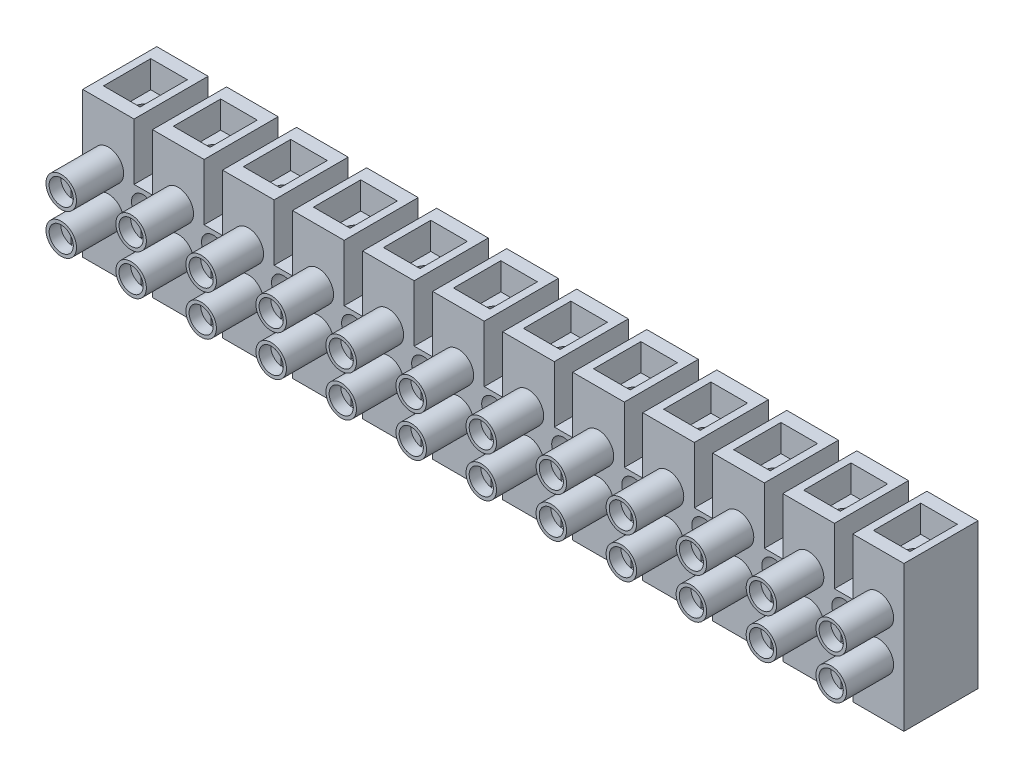
SolidWorks part; units mm, degrees
ref_plane "Front Plane" through (0, 0, 0) normal (0, 0, 1) x (1, 0, 0)
ref_plane "Top Plane" through (0, 0, 0) normal (0, 1, 0) x (1, 0, 0)
ref_plane "Right Plane" through (0, 0, 0) normal (1, 0, 0) x (0, 0, -1)
sketch "Sketch1" plane through (0, 0, 0) normal (0, 0, 1) x (1, 0, 0)
  line L1 (0, 16.9545) -> (95.758, 16.9545)
  line L2 (0, 16.9545) -> (0, 0)
  line L3 (0, 0) -> (95.758, 0)
  line L4 (95.758, 16.9545) -> (95.758, 0)
  dimension "D1" = 95.758
  dimension "D2" = 16.9545
extrude "Boss-Extrude1" add sketch "Sketch1" along normal blind 8.636
sketch "Sketch2" plane through (0, 0, 8.636) normal (0, 0, 1) x (1, 0, 0)
  line L0 (0, 8.4773) -> (95.758, 8.4773) construction
  line L1 (0, 16.9545) -> (0, 0) construction
  line L2 (95.758, 0) -> (95.758, 16.9545) construction
  line L3 (22.3202, 16.9545) -> (24.4666, 16.9545)
  line L4 (5.988, 16.9545) -> (8.1343, 16.9545)
  line L5 (5.988, 16.9545) -> (5.9881, 10.3505)
  line L6 (5.9881, 10.3505) -> (8.1343, 10.3505)
  line L7 (8.1343, 16.9545) -> (8.1343, 10.3505)
  line L8 (14.1542, 16.9545) -> (16.3005, 16.9545)
  line L9 (95.758, 16.9545) -> (0, 16.9545) construction
  line L10 (7.0612, 16.9545) -> (7.0612, 0) construction
  line L11 (15.2273, 16.9545) -> (15.2273, 0) construction
  line L12 (23.3934, 16.9545) -> (23.3934, 0) construction
  line L13 (31.5595, 16.9545) -> (31.5595, 0) construction
  line L14 (39.7256, 16.9545) -> (39.7256, 0) construction
  line L15 (47.8917, 16.9545) -> (47.8917, 0) construction
  line L16 (56.0578, 16.9545) -> (56.0578, 0) construction
  line L17 (64.2239, 16.9545) -> (64.2239, 0) construction
  line L18 (72.39, 16.9545) -> (72.39, 0) construction
  line L19 (88.7222, 16.9545) -> (88.7222, 0) construction
  line L20 (80.5561, 16.9545) -> (80.5561, 0) construction
  line L21 (0, 0) -> (95.758, 0) construction
  line L22 (14.1542, 16.9545) -> (14.1542, 10.3505)
  line L23 (14.1542, 10.3505) -> (16.3005, 10.3505)
  line L24 (16.3005, 16.9545) -> (16.3005, 10.3505)
  line L25 (22.3202, 16.9545) -> (22.3203, 10.3505)
  line L26 (22.3203, 10.3505) -> (24.4666, 10.3505)
  line L27 (24.4666, 16.9545) -> (24.4666, 10.3505)
  line L28 (30.4864, 16.9545) -> (32.6326, 16.9545)
  line L29 (30.4864, 16.9545) -> (30.4864, 10.3505)
  line L30 (30.4864, 10.3505) -> (32.6327, 10.3505)
  line L31 (32.6326, 16.9545) -> (32.6327, 10.3505)
  line L32 (38.6525, 16.9545) -> (40.7988, 16.9545)
  line L33 (38.6525, 16.9545) -> (38.6525, 10.3505)
  line L34 (38.6525, 10.3505) -> (40.7988, 10.3505)
  line L35 (40.7988, 16.9545) -> (40.7988, 10.3505)
  line L36 (46.8186, 16.9545) -> (48.9648, 16.9545)
  line L37 (46.8186, 16.9545) -> (46.8186, 10.3505)
  line L38 (46.8186, 10.3505) -> (48.9649, 10.3505)
  line L39 (48.9648, 16.9545) -> (48.9649, 10.3505)
  line L40 (54.9847, 16.9545) -> (57.131, 16.9545)
  line L41 (54.9847, 16.9545) -> (54.9847, 10.3505)
  line L42 (54.9847, 10.3505) -> (57.131, 10.3505)
  line L43 (57.131, 16.9545) -> (57.131, 10.3505)
  line L44 (63.1508, 16.9545) -> (65.2971, 16.9545)
  line L45 (63.1508, 16.9545) -> (63.1508, 10.3505)
  line L46 (63.1508, 10.3505) -> (65.2971, 10.3505)
  line L47 (65.2971, 16.9545) -> (65.2971, 10.3505)
  line L48 (71.3169, 16.9545) -> (73.4631, 16.9545)
  line L49 (71.3169, 16.9545) -> (71.3169, 10.3505)
  line L50 (71.3169, 10.3505) -> (73.4631, 10.3505)
  line L51 (73.4631, 16.9545) -> (73.4631, 10.3505)
  line L52 (79.483, 16.9545) -> (81.6292, 16.9545)
  line L53 (79.483, 16.9545) -> (79.483, 10.3505)
  line L54 (79.483, 10.3505) -> (81.6293, 10.3505)
  line L55 (81.6292, 16.9545) -> (81.6293, 10.3505)
  line L56 (87.6491, 16.9545) -> (89.7953, 16.9545)
  line L57 (87.6491, 16.9545) -> (87.6491, 10.3505)
  line L58 (87.6491, 10.3505) -> (89.7953, 10.3505)
  line L59 (89.7953, 16.9545) -> (89.7953, 10.3505)
  line L60 (5.988, 6.604) -> (8.1343, 6.604)
  line L61 (5.988, 6.604) -> (5.9881, 0)
  line L62 (5.9881, 0) -> (8.1343, 0)
  line L63 (8.1343, 6.604) -> (8.1343, 0)
  line L64 (14.1542, 6.604) -> (16.3005, 6.604)
  line L65 (14.1542, 6.604) -> (14.1542, 0)
  line L66 (14.1542, 0) -> (16.3005, 0)
  line L67 (16.3005, 6.604) -> (16.3005, 0)
  line L68 (22.3203, 6.604) -> (24.4666, 6.604)
  line L69 (22.3203, 6.604) -> (22.3203, 0)
  line L70 (22.3203, 0) -> (24.4666, 0)
  line L71 (24.4666, 6.604) -> (24.4666, 0)
  line L72 (30.4864, 6.604) -> (32.6326, 6.604)
  line L73 (30.4864, 6.604) -> (30.4864, 0)
  line L74 (30.4864, 0) -> (32.6326, 0)
  line L75 (32.6326, 6.604) -> (32.6326, 0)
  line L76 (38.6525, 6.604) -> (40.7987, 6.604)
  line L77 (38.6525, 6.604) -> (38.6525, 0)
  line L78 (38.6525, 0) -> (40.7987, 0)
  line L79 (40.7987, 6.604) -> (40.7987, 0)
  line L80 (48.9649, 6.604) -> (46.8186, 6.604)
  line L81 (48.9649, 6.604) -> (48.9649, 0)
  line L82 (48.9649, 0) -> (46.8186, 0)
  line L83 (46.8186, 6.604) -> (46.8186, 0)
  line L84 (57.131, 6.604) -> (54.9847, 6.604)
  line L85 (57.131, 6.604) -> (57.131, 0)
  line L86 (57.131, 0) -> (54.9847, 0)
  line L87 (54.9847, 6.604) -> (54.9847, 0)
  line L88 (63.1508, 6.604) -> (65.2971, 6.604)
  line L89 (63.1508, 6.604) -> (63.1508, 0)
  line L90 (63.1508, 0) -> (65.2971, 0)
  line L91 (65.2971, 6.604) -> (65.2971, 0)
  line L92 (71.3169, 6.604) -> (73.4631, 6.604)
  line L93 (71.3169, 6.604) -> (71.3169, 0)
  line L94 (71.3169, 0) -> (73.4632, 0)
  line L95 (73.4631, 6.604) -> (73.4632, 0)
  line L96 (79.483, 6.604) -> (81.6292, 6.604)
  line L97 (79.483, 6.604) -> (79.483, 0)
  line L98 (79.483, 0) -> (81.6293, 0)
  line L99 (81.6292, 6.604) -> (81.6293, 0)
  line L100 (89.7953, 6.604) -> (87.6491, 6.604)
  line L101 (89.7953, 6.604) -> (89.7953, 0)
  line L102 (89.7953, 0) -> (87.6491, 0)
  line L103 (87.6491, 6.604) -> (87.6491, 0)
  circle A0 centre (15.2273, 8.4773) radius 1.3716
  circle A1 centre (23.3934, 8.4773) radius 1.3716
  circle A2 centre (31.5595, 8.4773) radius 1.3716
  circle A3 centre (39.7256, 8.4773) radius 1.3716
  circle A4 centre (47.8917, 8.4773) radius 1.3716
  circle A5 centre (56.0578, 8.4773) radius 1.3716
  circle A6 centre (7.0612, 8.4773) radius 1.3716
  circle A7 centre (64.2239, 8.4773) radius 1.3716
  circle A8 centre (72.39, 8.4773) radius 1.3716
  circle A9 centre (80.5561, 8.4773) radius 1.3716
  circle A10 centre (88.7222, 8.4773) radius 1.3716
  dimension "D1" = 2.7432
  dimension "D2" = 7.0358
  dimension "D3" = 8.1661
  dimension "D4" = 8.1661
  dimension "D5" = 8.1661
  dimension "D6" = 8.1661
  dimension "D7" = 8.1661
  dimension "D8" = 8.1661
  dimension "D9" = 8.1661
  dimension "D10" = 8.1661
  dimension "D11" = 8.1661
  dimension "D12" = 8.1661
  dimension "D13" = 2.1463
  dimension "D14" = 6.604
extrude "Cut-Extrude2" cut sketch "Sketch2" against normal up to surface (8.636 mm away) up to face at (47.879, 8.4773, 0)
sketch "Sketch3" plane through (0, 0, 8.636) normal (0, 0, 1) x (1, 0, 0)
  line L0 (0, 6.1087) -> (95.758, 6.1087) construction
  line L1 (79.483, 16.9545) -> (73.4631, 16.9545) construction
  line L2 (0, 16.9545) -> (0, 0) construction
  line L3 (95.758, 0) -> (95.758, 16.9545) construction
  line L4 (95.758, 10.8458) -> (0, 10.8458) construction
  line L5 (47.879, 10.8458) -> (47.879, 6.1087) construction
  line L6 (95.758, 8.4773) -> (0, 8.4773) construction
  line L7 (92.7767, 16.9545) -> (92.7767, 0) construction
  line L8 (84.6392, 16.9545) -> (84.6392, 0) construction
  line L9 (76.4731, 16.9545) -> (76.4731, 0) construction
  line L10 (68.307, 16.9545) -> (68.307, 0) construction
  line L11 (60.1409, 16.9545) -> (60.1409, 0) construction
  line L12 (51.9748, 16.9545) -> (51.9748, 0) construction
  line L13 (43.8087, 16.9545) -> (43.8087, 0) construction
  line L14 (35.6425, 16.9545) -> (35.6425, 0) construction
  line L15 (27.4765, 16.9545) -> (27.4765, 0) construction
  line L16 (19.3103, 16.9545) -> (19.3104, 0) construction
  line L17 (11.1442, 16.9545) -> (11.1443, 0) construction
  line L18 (2.994, 16.9545) -> (2.994, 0) construction
  line L19 (5.988, 16.9545) -> (0, 16.9545) construction
  line L20 (0, 0) -> (5.9881, 0) construction
  line L21 (14.1542, 16.9545) -> (8.1343, 16.9545) construction
  line L22 (8.1343, 0) -> (14.1542, 0) construction
  line L23 (22.3202, 16.9545) -> (16.3005, 16.9545) construction
  line L24 (16.3005, 0) -> (22.3203, 0) construction
  line L25 (30.4864, 16.9545) -> (24.4666, 16.9545) construction
  line L26 (24.4666, 0) -> (30.4864, 0) construction
  line L27 (38.6525, 16.9545) -> (32.6326, 16.9545) construction
  line L28 (32.6326, 0) -> (38.6525, 0) construction
  line L29 (46.8186, 16.9545) -> (40.7988, 16.9545) construction
  line L30 (40.7987, 0) -> (46.8186, 0) construction
  line L31 (54.9847, 16.9545) -> (48.9648, 16.9545) construction
  line L32 (48.9649, 0) -> (54.9847, 0) construction
  line L33 (63.1508, 16.9545) -> (57.131, 16.9545) construction
  line L34 (57.131, 0) -> (63.1508, 0) construction
  line L35 (71.3169, 16.9545) -> (65.2971, 16.9545) construction
  line L36 (65.2971, 0) -> (71.3169, 0) construction
  line L37 (73.4632, 0) -> (79.483, 0) construction
  line L38 (87.6491, 16.9545) -> (81.6292, 16.9545) construction
  line L39 (81.6293, 0) -> (87.6491, 0) construction
  line L40 (95.758, 16.9545) -> (89.7953, 16.9545) construction
  line L41 (89.7953, 0) -> (95.758, 0) construction
  circle A0 centre (92.7767, 6.1087) radius 1.778
  circle A1 centre (11.1443, 10.8458) radius 1.778
  circle A2 centre (19.3103, 10.8458) radius 1.778
  circle A3 centre (27.4765, 10.8458) radius 1.778
  circle A4 centre (35.6425, 10.8458) radius 1.778
  circle A5 centre (43.8087, 10.8458) radius 1.778
  circle A6 centre (51.9748, 10.8458) radius 1.778
  circle A7 centre (60.1409, 10.8458) radius 1.778
  circle A8 centre (68.307, 10.8458) radius 1.778
  circle A9 centre (76.4731, 10.8458) radius 1.778
  circle A10 centre (84.6392, 10.8458) radius 1.778
  circle A11 centre (92.7767, 10.8458) radius 1.778
  circle A12 centre (2.994, 10.8458) radius 1.778
  circle A13 centre (2.994, 6.1087) radius 1.778
  circle A14 centre (11.1443, 6.1087) radius 1.778
  circle A15 centre (19.3103, 6.1087) radius 1.778
  circle A16 centre (27.4765, 6.1087) radius 1.778
  circle A17 centre (35.6426, 6.1087) radius 1.778
  circle A18 centre (43.8087, 6.1087) radius 1.778
  circle A19 centre (51.9748, 6.1087) radius 1.778
  circle A20 centre (60.1409, 6.1087) radius 1.778
  circle A21 centre (68.307, 6.1087) radius 1.778
  circle A22 centre (76.4731, 6.1087) radius 1.778
  circle A23 centre (84.6392, 6.1087) radius 1.778
  point P16 (47.879, 8.4773)
  dimension "D1" = 3.556
  dimension "D2" = 4.7371
extrude "Boss-Extrude2" add sketch "Sketch3" along normal blind 5.4991
sketch "Sketch4" plane through (0, 0, 14.1351) normal (0, 0, 1) x (1, 0, 0)
  circle A0 centre (11.1443, 6.1087) radius 1.4097
  circle A1 centre (19.3103, 6.1087) radius 1.4097
  circle A2 centre (27.4765, 6.1087) radius 1.4097
  circle A3 centre (35.6426, 6.1087) radius 1.4097
  circle A4 centre (43.8087, 6.1087) radius 1.4097
  circle A5 centre (51.9748, 6.1087) radius 1.4097
  circle A6 centre (60.1409, 6.1087) radius 1.4097
  circle A7 centre (68.307, 6.1087) radius 1.4097
  circle A8 centre (76.4731, 6.1087) radius 1.4097
  circle A9 centre (84.6392, 6.1087) radius 1.4097
  circle A10 centre (92.7767, 6.1087) radius 1.4097
  circle A11 centre (92.7767, 10.8458) radius 1.4097
  circle A12 centre (84.6392, 10.8458) radius 1.4097
  circle A13 centre (76.4731, 10.8458) radius 1.4097
  circle A14 centre (68.307, 10.8458) radius 1.4097
  circle A15 centre (60.1409, 10.8458) radius 1.4097
  circle A16 centre (51.9748, 10.8458) radius 1.4097
  circle A17 centre (43.8087, 10.8458) radius 1.4097
  circle A18 centre (35.6425, 10.8458) radius 1.4097
  circle A19 centre (27.4765, 10.8458) radius 1.4097
  circle A20 centre (19.3103, 10.8458) radius 1.4097
  circle A21 centre (11.1443, 10.8458) radius 1.4097
  circle A22 centre (2.994, 10.8458) radius 1.4097
  circle A23 centre (2.994, 6.1087) radius 1.4097
  circle A26 centre (92.7767, 10.8458) radius 1.778 construction
  circle A27 centre (84.6392, 10.8458) radius 1.778 construction
  circle A28 centre (76.4731, 10.8458) radius 1.778 construction
  circle A29 centre (68.307, 10.8458) radius 1.778 construction
  circle A30 centre (60.1409, 10.8458) radius 1.778 construction
  circle A31 centre (51.9748, 10.8458) radius 1.778 construction
  circle A32 centre (43.8087, 10.8458) radius 1.778 construction
  circle A33 centre (35.6425, 10.8458) radius 1.778 construction
  circle A34 centre (27.4765, 10.8458) radius 1.778 construction
  circle A35 centre (19.3103, 10.8458) radius 1.778 construction
  circle A36 centre (11.1443, 10.8458) radius 1.778 construction
  circle A37 centre (2.994, 10.8458) radius 1.778 construction
  circle A38 centre (2.994, 6.1087) radius 1.778 construction
  circle A39 centre (11.1443, 6.1087) radius 1.778 construction
  circle A40 centre (19.3103, 6.1087) radius 1.778 construction
  circle A41 centre (27.4765, 6.1087) radius 1.778 construction
  circle A42 centre (35.6426, 6.1087) radius 1.778 construction
  circle A43 centre (43.8087, 6.1087) radius 1.778 construction
  circle A44 centre (51.9748, 6.1087) radius 1.778 construction
  circle A45 centre (60.1409, 6.1087) radius 1.778 construction
  circle A46 centre (68.307, 6.1087) radius 1.778 construction
  circle A47 centre (76.4731, 6.1087) radius 1.778 construction
  circle A48 centre (84.6392, 6.1087) radius 1.778 construction
  circle A49 centre (92.7767, 6.1087) radius 1.778 construction
  dimension "D1" = 2.8194
extrude "Cut-Extrude3" cut sketch "Sketch4" against normal blind 1.3589
sketch "Sketch5" plane through (0, 0, 0) normal (0, -1, 0) x (1, 0, 0)
  line L0 (27.4765, 8.636) -> (27.4765, 0) construction
  line L1 (35.6425, 8.636) -> (35.6425, 0) construction
  line L2 (43.8087, 8.636) -> (43.8087, 0) construction
  line L3 (51.9748, 8.636) -> (51.9748, 0) construction
  line L4 (60.1409, 8.636) -> (60.1409, 0) construction
  line L5 (68.307, 8.636) -> (68.307, 0) construction
  line L6 (76.4731, 8.636) -> (76.4731, 0) construction
  line L7 (84.6392, 8.636) -> (84.6392, 0) construction
  line L8 (92.7767, 8.636) -> (92.7767, 0) construction
  line L9 (19.3104, 8.636) -> (19.3104, 0) construction
  line L10 (11.1443, 8.636) -> (11.1443, 0) construction
  line L11 (2.994, 8.636) -> (2.994, 0) construction
  line L12 (0, 8.636) -> (5.9881, 8.636) construction
  line L13 (0, 0) -> (5.9881, 0) construction
  line L14 (8.1343, 8.636) -> (14.1542, 8.636) construction
  line L15 (8.1343, 0) -> (14.1542, 0) construction
  line L16 (16.3005, 8.636) -> (22.3203, 8.636) construction
  line L17 (16.3005, 0) -> (22.3203, 0) construction
  line L18 (24.4666, 8.636) -> (30.4864, 8.636) construction
  line L19 (24.4666, 0) -> (30.4864, 0) construction
  line L20 (32.6326, 8.636) -> (38.6525, 8.636) construction
  line L21 (40.7987, 8.636) -> (46.8186, 8.636) construction
  line L22 (48.9649, 8.636) -> (54.9847, 8.636) construction
  line L23 (57.131, 8.636) -> (63.1508, 8.636) construction
  line L24 (65.2971, 8.636) -> (71.3169, 8.636) construction
  line L25 (73.4632, 8.636) -> (79.483, 8.636) construction
  line L26 (81.6293, 8.636) -> (87.6491, 8.636) construction
  line L27 (89.7953, 8.636) -> (95.758, 8.636) construction
  line L28 (32.6326, 0) -> (38.6525, 0) construction
  line L29 (40.7987, 0) -> (46.8186, 0) construction
  line L30 (48.9649, 0) -> (54.9847, 0) construction
  line L31 (57.131, 0) -> (63.1508, 0) construction
  line L32 (65.2971, 0) -> (71.3169, 0) construction
  line L33 (73.4632, 0) -> (79.483, 0) construction
  line L34 (81.6293, 0) -> (87.6491, 0) construction
  line L35 (89.7953, 0) -> (95.758, 0) construction
  line L36 (9.0107, 7.0739) -> (13.2779, 7.0739)
  line L37 (0.8604, 7.0739) -> (5.1276, 7.0739)
  line L38 (0.8604, 7.0739) -> (0.8604, 1.5621)
  line L39 (0.8604, 1.5621) -> (5.1276, 1.5621)
  line L40 (5.1276, 7.0739) -> (5.1276, 1.5621)
  line L41 (9.0107, 7.0739) -> (9.0107, 1.5621)
  line L42 (9.0107, 1.5621) -> (13.2779, 1.5621)
  line L43 (13.2779, 7.0739) -> (13.2779, 1.5621)
  line L44 (25.3429, 7.0739) -> (29.6101, 7.0739)
  line L45 (25.3429, 7.0739) -> (25.3429, 1.5621)
  line L46 (25.3429, 1.5621) -> (29.6101, 1.5621)
  line L47 (29.6101, 7.0739) -> (29.6101, 1.5621)
  line L48 (33.5089, 7.0739) -> (37.7761, 7.0739)
  line L49 (33.5089, 7.0739) -> (33.5089, 1.5621)
  line L50 (33.5089, 1.5621) -> (37.7761, 1.5621)
  line L51 (37.7761, 7.0739) -> (37.7761, 1.5621)
  line L52 (41.6751, 7.0739) -> (45.9423, 7.0739)
  line L53 (41.6751, 7.0739) -> (41.6751, 1.5621)
  line L54 (41.6751, 1.5621) -> (45.9423, 1.5621)
  line L55 (45.9423, 7.0739) -> (45.9423, 1.5621)
  line L56 (17.1768, 7.0739) -> (21.444, 7.0739)
  line L57 (17.1768, 7.0739) -> (17.1768, 1.5621)
  line L58 (17.1768, 1.5621) -> (21.444, 1.5621)
  line L59 (21.444, 7.0739) -> (21.444, 1.5621)
  line L60 (66.1734, 7.0739) -> (70.4406, 7.0739)
  line L61 (66.1734, 7.0739) -> (66.1734, 1.5621)
  line L62 (66.1734, 1.5621) -> (70.4406, 1.5621)
  line L63 (70.4406, 7.0739) -> (70.4406, 1.5621)
  line L64 (74.3395, 7.0739) -> (78.6067, 7.0739)
  line L65 (74.3395, 7.0739) -> (74.3395, 1.5621)
  line L66 (74.3395, 1.5621) -> (78.6067, 1.5621)
  line L67 (78.6067, 7.0739) -> (78.6067, 1.5621)
  line L68 (82.5056, 7.0739) -> (86.7728, 7.0739)
  line L69 (82.5056, 7.0739) -> (82.5056, 1.5621)
  line L70 (82.5056, 1.5621) -> (86.7728, 1.5621)
  line L71 (86.7728, 7.0739) -> (86.7728, 1.5621)
  line L72 (49.8411, 7.0739) -> (54.1084, 7.0739)
  line L73 (49.8411, 7.0739) -> (49.8411, 1.5621)
  line L74 (49.8411, 1.5621) -> (54.1084, 1.5621)
  line L75 (54.1084, 7.0739) -> (54.1084, 1.5621)
  line L76 (90.6431, 7.0739) -> (94.9103, 7.0739)
  line L77 (90.6431, 7.0739) -> (90.6431, 1.5621)
  line L78 (90.6431, 1.5621) -> (94.9103, 1.5621)
  line L79 (94.9103, 7.0739) -> (94.9103, 1.5621)
  line L80 (58.0073, 7.0739) -> (62.2745, 7.0739)
  line L81 (58.0073, 7.0739) -> (58.0073, 1.5621)
  line L82 (58.0073, 1.5621) -> (62.2745, 1.5621)
  line L83 (62.2745, 7.0739) -> (62.2745, 1.5621)
  line L92 (0, 4.318) -> (5.9881, 4.318) construction
  line L93 (8.1344, 4.318) -> (14.1542, 4.318) construction
  line L94 (16.3005, 4.318) -> (22.3203, 4.318) construction
  line L95 (24.4666, 4.318) -> (30.4864, 4.318) construction
  line L96 (32.6326, 4.318) -> (38.6525, 4.318) construction
  line L97 (40.7987, 4.318) -> (46.8186, 4.318) construction
  line L98 (48.9649, 4.318) -> (54.9847, 4.318) construction
  line L99 (57.131, 4.318) -> (63.1508, 4.318) construction
  line L100 (65.2971, 4.318) -> (71.3169, 4.318) construction
  line L101 (73.4631, 4.318) -> (79.483, 4.318) construction
  line L102 (81.6293, 4.318) -> (87.6491, 4.318) construction
  line L103 (89.7953, 4.318) -> (95.758, 4.318) construction
  line L104 (0, 8.636) -> (0, 0) construction
  line L105 (5.9881, 0) -> (5.9881, 8.636) construction
  line L106 (8.1344, 0) -> (8.1344, 8.636) construction
  line L107 (14.1542, 0) -> (14.1542, 8.636) construction
  line L108 (16.3005, 0) -> (16.3005, 8.636) construction
  line L109 (22.3203, 0) -> (22.3203, 8.636) construction
  line L110 (24.4666, 0) -> (24.4666, 8.636) construction
  line L111 (30.4864, 0) -> (30.4864, 8.636) construction
  line L112 (32.6326, 0) -> (32.6326, 8.636) construction
  line L113 (38.6525, 0) -> (38.6525, 8.636) construction
  line L114 (40.7987, 0) -> (40.7987, 8.636) construction
  line L115 (46.8186, 0) -> (46.8186, 8.636) construction
  line L116 (48.9649, 0) -> (48.9649, 8.636) construction
  line L117 (54.9847, 0) -> (54.9847, 8.636) construction
  line L118 (57.131, 0) -> (57.131, 8.636) construction
  line L119 (63.1508, 0) -> (63.1508, 8.636) construction
  line L120 (65.2971, 0) -> (65.2971, 8.636) construction
  line L121 (71.3169, 0) -> (71.3169, 8.636) construction
  line L122 (73.4631, 0) -> (73.4631, 8.636) construction
  line L123 (79.483, 0) -> (79.483, 8.636) construction
  line L124 (81.6293, 0) -> (81.6293, 8.636) construction
  line L125 (87.6491, 0) -> (87.6491, 8.636) construction
  line L126 (95.758, 8.636) -> (95.758, 0) construction
  line L127 (89.7953, 0) -> (89.7953, 8.636) construction
  point P80 (11.1442, 7.0739)
  point P81 (13.2779, 4.318)
  point P87 (27.4765, 7.0739)
  point P89 (29.6101, 4.318)
  point P94 (35.6425, 7.0739)
  point P96 (37.7761, 4.318)
  point P101 (43.8087, 7.0739)
  point P103 (45.9423, 4.318)
  point P108 (19.3104, 7.0739)
  point P110 (21.444, 4.318)
  point P115 (68.307, 7.0739)
  point P117 (70.4406, 4.318)
  point P122 (76.4731, 7.0739)
  point P124 (78.6067, 4.318)
  point P128 (2.994, 7.0739)
  point P202 (5.1276, 4.318)
  point P205 (84.6392, 7.0739)
  point P207 (86.7728, 4.318)
  point P212 (51.9748, 7.0739)
  point P214 (54.1084, 4.318)
  point P219 (92.7767, 7.0739)
  point P221 (94.9103, 4.318)
  point P226 (60.1409, 7.0739)
  point P228 (62.2745, 4.318)
  dimension "D1" = 5.5118
  dimension "D2" = 4.2672
extrude "Cut-Extrude4" cut sketch "Sketch5" against normal blind 3.1496
sketch "Sketch6" plane through (0, 16.9545, 0) normal (0, 1, 0) x (1, 0, 0)
  line L0 (8.1343, -4.318) -> (14.1541, -4.318) construction
  line L1 (16.3005, -4.318) -> (22.3203, -4.318) construction
  line L2 (24.4666, -4.318) -> (30.4864, -4.318) construction
  line L3 (32.6326, -4.318) -> (38.6525, -4.318) construction
  line L4 (40.7988, -4.318) -> (46.8186, -4.318) construction
  line L5 (48.9648, -4.318) -> (54.9847, -4.318) construction
  line L6 (57.131, -4.318) -> (63.1508, -4.318) construction
  line L7 (65.2971, -4.318) -> (71.3169, -4.318) construction
  line L8 (73.4631, -4.318) -> (79.483, -4.318) construction
  line L9 (81.6292, -4.318) -> (87.6491, -4.318) construction
  line L10 (89.7953, -4.318) -> (95.758, -4.318) construction
  line L11 (2.994, 0) -> (2.994, -8.636) construction
  line L12 (14.1541, 0) -> (14.1541, -8.636) construction
  line L13 (0.8604, -1.5621) -> (5.1276, -1.5621)
  line L14 (0.8604, -1.5621) -> (0.8604, -7.0739)
  line L15 (0.8604, -7.0739) -> (5.1276, -7.0739)
  line L16 (5.1276, -1.5621) -> (5.1276, -7.0739)
  line L17 (8.1343, 0) -> (8.1343, -8.636) construction
  line L18 (16.3005, 0) -> (16.3005, -8.636) construction
  line L19 (22.3203, 0) -> (22.3203, -8.636) construction
  line L20 (24.4666, 0) -> (24.4666, -8.636) construction
  line L21 (30.4864, 0) -> (30.4864, -8.636) construction
  line L22 (32.6326, 0) -> (32.6326, -8.636) construction
  line L23 (38.6525, 0) -> (38.6525, -8.636) construction
  line L24 (40.7988, 0) -> (40.7988, -8.636) construction
  line L25 (46.8186, 0) -> (46.8186, -8.636) construction
  line L26 (48.9648, 0) -> (48.9648, -8.636) construction
  line L27 (54.9847, 0) -> (54.9847, -8.636) construction
  line L28 (57.131, 0) -> (57.131, -8.636) construction
  line L29 (63.1508, 0) -> (63.1508, -8.636) construction
  line L30 (65.2971, 0) -> (65.2971, -8.636) construction
  line L31 (71.3169, 0) -> (71.3169, -8.636) construction
  line L32 (25.3429, -1.5621) -> (29.6101, -1.5621)
  line L33 (73.4631, 0) -> (73.4631, -8.636) construction
  line L34 (79.483, 0) -> (79.483, -8.636) construction
  line L35 (81.6292, 0) -> (81.6292, -8.636) construction
  line L36 (87.6491, 0) -> (87.6491, -8.636) construction
  line L37 (89.7953, 0) -> (89.7953, -8.636) construction
  line L38 (95.758, -8.636) -> (95.758, 0) construction
  line L39 (11.1442, 0) -> (11.1442, -8.636) construction
  line L40 (19.3103, 0) -> (19.3103, -8.636) construction
  line L41 (27.4764, 0) -> (27.4764, -8.636) construction
  line L42 (35.6425, 0) -> (35.6425, -8.636) construction
  line L43 (43.8087, 0) -> (43.8087, -8.636) construction
  line L44 (51.9747, 0) -> (51.9747, -8.636) construction
  line L45 (68.3069, 0) -> (68.3069, -8.636) construction
  line L46 (84.6392, 0) -> (84.6392, -8.636) construction
  line L47 (92.7767, 0) -> (92.7767, -8.636) construction
  line L48 (76.4731, 0) -> (76.4731, -8.636) construction
  line L49 (60.1409, 0) -> (60.1409, -8.636) construction
  line L50 (14.1541, -8.636) -> (8.1343, -8.636) construction
  line L51 (14.1541, 0) -> (8.1343, 0) construction
  line L52 (22.3202, -8.636) -> (16.3005, -8.636) construction
  line L53 (30.4864, -8.636) -> (24.4666, -8.636) construction
  line L54 (38.6525, -8.636) -> (32.6326, -8.636) construction
  line L55 (46.8186, -8.636) -> (40.7988, -8.636) construction
  line L56 (54.9847, -8.636) -> (48.9648, -8.636) construction
  line L57 (63.1508, -8.636) -> (57.131, -8.636) construction
  line L58 (71.3169, -8.636) -> (65.2971, -8.636) construction
  line L59 (79.483, -8.636) -> (73.4631, -8.636) construction
  line L60 (0, -4.318) -> (5.988, -4.318) construction
  line L61 (87.6491, -8.636) -> (81.6292, -8.636) construction
  line L62 (95.758, -8.636) -> (89.7953, -8.636) construction
  line L63 (25.3429, -1.5621) -> (25.3429, -7.0739)
  line L64 (17.1767, -1.5621) -> (21.444, -1.5621)
  line L65 (17.1767, -1.5621) -> (17.1767, -7.0739)
  line L66 (17.1767, -7.0739) -> (21.444, -7.0739)
  line L67 (21.444, -1.5621) -> (21.444, -7.0739)
  line L68 (25.3429, -7.0739) -> (29.6101, -7.0739)
  line L69 (29.6101, -1.5621) -> (29.6101, -7.0739)
  line L70 (9.0106, -1.5621) -> (13.2778, -1.5621)
  line L71 (9.0106, -1.5621) -> (9.0106, -7.0739)
  line L72 (9.0106, -7.0739) -> (13.2778, -7.0739)
  line L73 (13.2778, -1.5621) -> (13.2778, -7.0739)
  line L74 (5.988, -8.636) -> (0, -8.636) construction
  line L75 (5.988, 0) -> (0, 0) construction
  line L76 (0, -8.636) -> (0, 0) construction
  line L77 (5.9881, 0) -> (5.9881, -8.636) construction
  line L78 (74.3395, -1.5621) -> (78.6067, -1.5621)
  line L79 (74.3395, -1.5621) -> (74.3395, -7.0739)
  line L80 (74.3395, -7.0739) -> (78.6067, -7.0739)
  line L81 (78.6067, -1.5621) -> (78.6067, -7.0739)
  line L82 (33.5089, -1.5621) -> (37.7761, -1.5621)
  line L83 (33.5089, -1.5621) -> (33.5089, -7.0739)
  line L84 (33.5089, -7.0739) -> (37.7761, -7.0739)
  line L85 (37.7761, -1.5621) -> (37.7761, -7.0739)
  line L86 (41.6751, -1.5621) -> (45.9423, -1.5621)
  line L87 (41.6751, -1.5621) -> (41.6751, -7.0739)
  line L88 (41.6751, -7.0739) -> (45.9423, -7.0739)
  line L89 (45.9423, -1.5621) -> (45.9423, -7.0739)
  line L90 (49.8411, -1.5621) -> (54.1084, -1.5621)
  line L91 (49.8411, -1.5621) -> (49.8411, -7.0739)
  line L92 (49.8411, -7.0739) -> (54.1084, -7.0739)
  line L93 (54.1084, -1.5621) -> (54.1084, -7.0739)
  line L94 (66.1733, -1.5621) -> (70.4406, -1.5621)
  line L95 (66.1733, -1.5621) -> (66.1733, -7.0739)
  line L96 (66.1733, -7.0739) -> (70.4406, -7.0739)
  line L97 (70.4406, -1.5621) -> (70.4406, -7.0739)
  line L98 (90.6431, -1.5621) -> (94.9103, -1.5621)
  line L99 (90.6431, -1.5621) -> (90.6431, -7.0739)
  line L100 (90.6431, -7.0739) -> (94.9103, -7.0739)
  line L101 (94.9103, -1.5621) -> (94.9103, -7.0739)
  line L102 (82.5055, -1.5621) -> (86.7728, -1.5621)
  line L103 (82.5055, -1.5621) -> (82.5055, -7.0739)
  line L104 (82.5055, -7.0739) -> (86.7728, -7.0739)
  line L105 (86.7728, -1.5621) -> (86.7728, -7.0739)
  line L106 (58.0073, -1.5621) -> (62.2745, -1.5621)
  line L107 (58.0073, -1.5621) -> (58.0073, -7.0739)
  line L108 (58.0073, -7.0739) -> (62.2745, -7.0739)
  line L109 (62.2745, -1.5621) -> (62.2745, -7.0739)
  point P73 (2.994, -1.5621)
  point P98 (5.1276, -4.318)
  point P136 (19.3103, -1.5621)
  point P139 (21.4439, -4.318)
  point P140 (27.4765, -1.5621)
  point P141 (29.6101, -4.318)
  point P146 (11.1442, -1.5621)
  point P147 (13.2779, -4.318)
  point P152 (76.4731, -1.5621)
  point P153 (78.6067, -4.318)
  point P158 (35.6425, -1.5621)
  point P159 (37.7762, -4.318)
  point P164 (43.8087, -1.5621)
  point P165 (45.9423, -4.318)
  point P170 (51.9748, -1.5621)
  point P171 (54.1084, -4.318)
  point P176 (68.307, -1.5621)
  point P177 (70.4406, -4.318)
  point P182 (92.7767, -1.5621)
  point P183 (94.9103, -4.318)
  point P188 (84.6392, -1.5621)
  point P189 (86.7728, -4.318)
  point P194 (60.1409, -1.5621)
  point P195 (62.2745, -4.318)
  dimension "D1" = 5.5118
  dimension "D2" = 4.2672
extrude "Cut-Extrude5" cut sketch "Sketch6" against normal blind 3.1496
sketch "Sketch7" plane through (0, 3.1496, 0) normal (0, -1, 0) x (-1, 0, 0)
  line L0 (-2.994, -7.0739) -> (-2.994, -1.5621) construction
  line L1 (-11.1443, -7.0739) -> (-11.1443, -1.5621) construction
  line L2 (-19.3103, -7.0739) -> (-19.3104, -1.5621) construction
  line L3 (-27.4765, -7.0739) -> (-27.4765, -1.5621) construction
  line L4 (-35.6425, -7.0739) -> (-35.6425, -1.5621) construction
  line L5 (-43.8087, -7.0739) -> (-43.8087, -1.5621) construction
  line L6 (-51.9748, -7.0739) -> (-51.9748, -1.5621) construction
  line L7 (-60.1409, -7.0739) -> (-60.1409, -1.5621) construction
  line L8 (-68.307, -7.0739) -> (-68.307, -1.5621) construction
  line L9 (-76.4731, -7.0739) -> (-76.4731, -1.5621) construction
  line L10 (-84.6392, -7.0739) -> (-84.6392, -1.5621) construction
  line L11 (-92.7767, -7.0739) -> (-92.7767, -1.5621) construction
  line L12 (-0.8604, -1.5621) -> (-5.1276, -1.5621) construction
  line L13 (-5.1276, -7.0739) -> (-0.8604, -7.0739) construction
  line L14 (-9.0107, -1.5621) -> (-13.2779, -1.5621) construction
  line L15 (-13.2779, -7.0739) -> (-9.0107, -7.0739) construction
  line L16 (-21.444, -7.0739) -> (-17.1768, -7.0739) construction
  line L17 (-17.1768, -1.5621) -> (-21.444, -1.5621) construction
  line L18 (-25.3429, -1.5621) -> (-29.6101, -1.5621) construction
  line L19 (-29.6101, -7.0739) -> (-25.3429, -7.0739) construction
  line L20 (-37.7761, -7.0739) -> (-33.5089, -7.0739) construction
  line L21 (-33.5089, -1.5621) -> (-37.7761, -1.5621) construction
  line L22 (-41.6751, -1.5621) -> (-45.9423, -1.5621) construction
  line L23 (-45.9423, -7.0739) -> (-41.6751, -7.0739) construction
  line L24 (-54.1084, -7.0739) -> (-49.8411, -7.0739) construction
  line L25 (-49.8411, -1.5621) -> (-54.1084, -1.5621) construction
  line L26 (-58.0073, -1.5621) -> (-62.2745, -1.5621) construction
  line L27 (-62.2745, -7.0739) -> (-58.0073, -7.0739) construction
  line L28 (-70.4406, -7.0739) -> (-66.1734, -7.0739) construction
  line L29 (-66.1734, -1.5621) -> (-70.4406, -1.5621) construction
  line L30 (-74.3395, -1.5621) -> (-78.6067, -1.5621) construction
  line L31 (-78.6067, -7.0739) -> (-74.3395, -7.0739) construction
  line L32 (-86.7728, -7.0739) -> (-82.5056, -7.0739) construction
  line L33 (-82.5056, -1.5621) -> (-86.7728, -1.5621) construction
  line L34 (-94.9103, -7.0739) -> (-90.6431, -7.0739) construction
  line L35 (-90.6431, -1.5621) -> (-94.9103, -1.5621) construction
  circle A0 centre (-92.7767, -4.318) radius 1.4351
  circle A1 centre (-2.994, -4.318) radius 1.4351
  circle A2 centre (-11.1443, -4.318) radius 1.4351
  circle A3 centre (-19.3104, -4.318) radius 1.4351
  circle A4 centre (-27.4765, -4.318) radius 1.4351
  circle A5 centre (-35.6425, -4.318) radius 1.4351
  circle A6 centre (-43.8087, -4.318) radius 1.4351
  circle A7 centre (-51.9747, -4.318) radius 1.4351
  circle A8 centre (-60.1409, -4.318) radius 1.4351
  circle A9 centre (-68.307, -4.318) radius 1.4351
  circle A10 centre (-76.4731, -4.318) radius 1.4351
  circle A11 centre (-84.6392, -4.318) radius 1.4351
  dimension "D1" = 2.8702
extrude "Cut-Extrude6" cut sketch "Sketch7" against normal up to surface (10.6553 mm away) up to face at (27.4765, 13.8049, 4.318)
sketch "Sketch8" plane through (0, 0, 12.7762) normal (0, 0, 1) x (1, 0, 0)
  line L0 (0, 16.9545) -> (0, 0) construction
  line L1 (2.7596, 12.2359) -> (3.2284, 12.2359)
  line L2 (2.7596, 12.2359) -> (2.7596, 9.4557)
  line L3 (2.7596, 9.4557) -> (3.2284, 9.4557)
  line L4 (3.2284, 12.2359) -> (3.2284, 9.4557)
  line L5 (2.7596, 7.4988) -> (3.2284, 7.4988)
  line L6 (2.7596, 7.4988) -> (2.7596, 4.7186)
  line L7 (2.7596, 4.7186) -> (3.2284, 4.7186)
  line L8 (3.2284, 7.4988) -> (3.2284, 4.7186)
  line L9 (10.9098, 12.2359) -> (11.3787, 12.2359)
  line L10 (10.9098, 12.2359) -> (10.9098, 9.4557)
  line L11 (10.9098, 9.4557) -> (11.3787, 9.4557)
  line L12 (11.3787, 12.2359) -> (11.3787, 9.4557)
  line L13 (10.9098, 7.4988) -> (11.3787, 7.4988)
  line L14 (10.9098, 7.4988) -> (10.9098, 4.7186)
  line L15 (10.9098, 4.7186) -> (11.3787, 4.7186)
  line L16 (11.3787, 7.4988) -> (11.3787, 4.7186)
  line L17 (19.0759, 12.2359) -> (19.5448, 12.2359)
  line L18 (19.0759, 12.2359) -> (19.0759, 9.4557)
  line L19 (19.0759, 9.4557) -> (19.5448, 9.4557)
  line L20 (19.5448, 12.2359) -> (19.5448, 9.4557)
  line L21 (19.0759, 7.4988) -> (19.5448, 7.4988)
  line L22 (19.0759, 7.4988) -> (19.0759, 4.7186)
  line L23 (19.0759, 4.7186) -> (19.5448, 4.7186)
  line L24 (19.5448, 7.4988) -> (19.5448, 4.7186)
  line L25 (27.242, 12.2359) -> (27.7109, 12.2359)
  line L26 (27.242, 12.2359) -> (27.242, 9.4557)
  line L27 (27.242, 9.4557) -> (27.7109, 9.4557)
  line L28 (27.7109, 12.2359) -> (27.7109, 9.4557)
  line L29 (35.877, 12.2359) -> (35.4081, 12.2359)
  line L30 (35.877, 12.2359) -> (35.877, 9.4557)
  line L31 (35.877, 9.4557) -> (35.4081, 9.4557)
  line L32 (35.4081, 12.2359) -> (35.4081, 9.4557)
  line L33 (35.4081, 7.4988) -> (35.877, 7.4988)
  line L34 (35.4081, 7.4988) -> (35.4081, 4.7186)
  line L35 (35.4081, 4.7186) -> (35.877, 4.7186)
  line L36 (35.877, 7.4988) -> (35.877, 4.7186)
  line L37 (27.242, 7.4988) -> (27.7109, 7.4988)
  line L38 (27.242, 7.4988) -> (27.242, 4.7186)
  line L39 (27.242, 4.7186) -> (27.7109, 4.7186)
  line L40 (27.7109, 7.4988) -> (27.7109, 4.7186)
  line L41 (43.5742, 12.2359) -> (44.0431, 12.2359)
  line L42 (43.5742, 12.2359) -> (43.5742, 9.4557)
  line L43 (43.5742, 9.4557) -> (44.0431, 9.4557)
  line L44 (44.0431, 12.2359) -> (44.0431, 9.4557)
  line L45 (43.5742, 7.4988) -> (44.0431, 7.4988)
  line L46 (43.5742, 7.4988) -> (43.5742, 4.7186)
  line L47 (43.5742, 4.7186) -> (44.0431, 4.7186)
  line L48 (44.0431, 7.4988) -> (44.0431, 4.7186)
  line L49 (51.7403, 12.2359) -> (52.2092, 12.2359)
  line L50 (51.7403, 12.2359) -> (51.7403, 9.4557)
  line L51 (51.7403, 9.4557) -> (52.2092, 9.4557)
  line L52 (52.2092, 12.2359) -> (52.2092, 9.4557)
  line L53 (51.7403, 7.4988) -> (52.2092, 7.4988)
  line L54 (51.7403, 7.4988) -> (51.7403, 4.7186)
  line L55 (51.7403, 4.7186) -> (52.2092, 4.7186)
  line L56 (52.2092, 7.4988) -> (52.2092, 4.7186)
  line L57 (59.9064, 7.4988) -> (60.3753, 7.4988)
  line L58 (59.9064, 7.4988) -> (59.9064, 4.7186)
  line L59 (59.9064, 4.7186) -> (60.3753, 4.7186)
  line L60 (60.3753, 7.4988) -> (60.3753, 4.7186)
  line L61 (59.9064, 12.2359) -> (60.3753, 12.2359)
  line L62 (59.9064, 12.2359) -> (59.9064, 9.4557)
  line L63 (59.9064, 9.4557) -> (60.3753, 9.4557)
  line L64 (60.3753, 12.2359) -> (60.3753, 9.4557)
  line L65 (68.0725, 12.2359) -> (68.5414, 12.2359)
  line L66 (68.0725, 12.2359) -> (68.0725, 9.4557)
  line L67 (68.0725, 9.4557) -> (68.5414, 9.4557)
  line L68 (68.5414, 12.2359) -> (68.5414, 9.4557)
  line L69 (68.0725, 7.4988) -> (68.5414, 7.4988)
  line L70 (68.0725, 7.4988) -> (68.0725, 4.7186)
  line L71 (68.0725, 4.7186) -> (68.5414, 4.7186)
  line L72 (68.5414, 7.4988) -> (68.5414, 4.7186)
  line L73 (76.2386, 7.4988) -> (76.7075, 7.4988)
  line L74 (76.2386, 7.4988) -> (76.2386, 4.7186)
  line L75 (76.2386, 4.7186) -> (76.7075, 4.7186)
  line L76 (76.7075, 7.4988) -> (76.7075, 4.7186)
  line L77 (76.2386, 12.2359) -> (76.7075, 12.2359)
  line L78 (76.2386, 12.2359) -> (76.2386, 9.4557)
  line L79 (76.2386, 9.4557) -> (76.7075, 9.4557)
  line L80 (76.7075, 12.2359) -> (76.7075, 9.4557)
  line L81 (84.4047, 12.2359) -> (84.8736, 12.2359)
  line L82 (84.4047, 12.2359) -> (84.4047, 9.4557)
  line L83 (84.4047, 9.4557) -> (84.8736, 9.4557)
  line L84 (84.8736, 12.2359) -> (84.8736, 9.4557)
  line L85 (92.5423, 12.2359) -> (93.0111, 12.2359)
  line L86 (92.5423, 12.2359) -> (92.5423, 9.4557)
  line L87 (92.5423, 9.4557) -> (93.0111, 9.4557)
  line L88 (93.0111, 12.2359) -> (93.0111, 9.4557)
  line L89 (92.5423, 7.4988) -> (93.0111, 7.4988)
  line L90 (92.5423, 7.4988) -> (92.5423, 4.7186)
  line L91 (92.5423, 4.7186) -> (93.0111, 4.7186)
  line L92 (93.0111, 7.4988) -> (93.0111, 4.7186)
  line L93 (84.4047, 7.4988) -> (84.8736, 7.4988)
  line L94 (84.4047, 7.4988) -> (84.4047, 4.7186)
  line L95 (84.4047, 4.7186) -> (84.8736, 4.7186)
  line L96 (84.8736, 7.4988) -> (84.8736, 4.7186)
  circle A0 centre (2.994, 10.8458) radius 1.4097 construction
  circle A1 centre (2.994, 6.1087) radius 1.4097 construction
  circle A2 centre (35.6425, 10.8458) radius 1.4097 construction
  circle A3 centre (11.1443, 6.1087) radius 1.4097 construction
  circle A4 centre (11.1443, 10.8458) radius 1.4097 construction
  circle A5 centre (19.3103, 10.8458) radius 1.4097 construction
  circle A6 centre (19.3103, 6.1087) radius 1.4097 construction
  circle A7 centre (27.4765, 6.1087) radius 1.4097 construction
  circle A8 centre (27.4765, 10.8458) radius 1.4097 construction
  circle A9 centre (35.6426, 6.1087) radius 1.4097 construction
  circle A10 centre (43.8087, 10.8458) radius 1.4097 construction
  circle A11 centre (43.8087, 6.1087) radius 1.4097 construction
  circle A12 centre (51.9748, 10.8458) radius 1.4097 construction
  circle A13 centre (51.9748, 6.1087) radius 1.4097 construction
  circle A14 centre (60.1409, 10.8458) radius 1.4097 construction
  circle A15 centre (60.1409, 6.1087) radius 1.4097 construction
  circle A16 centre (68.307, 10.8458) radius 1.4097 construction
  circle A17 centre (68.307, 6.1087) radius 1.4097 construction
  circle A18 centre (76.4731, 6.1087) radius 1.4097 construction
  circle A19 centre (76.4731, 10.8458) radius 1.4097 construction
  circle A20 centre (84.6392, 6.1087) radius 1.4097 construction
  circle A21 centre (84.6392, 10.8458) radius 1.4097 construction
  circle A22 centre (92.7767, 6.1087) radius 1.4097 construction
  circle A23 centre (92.7767, 10.8458) radius 1.4097 construction
  dimension "D1" = 2.7801
extrude "Cut-Extrude7" cut sketch "Sketch8" against normal blind 0.508
